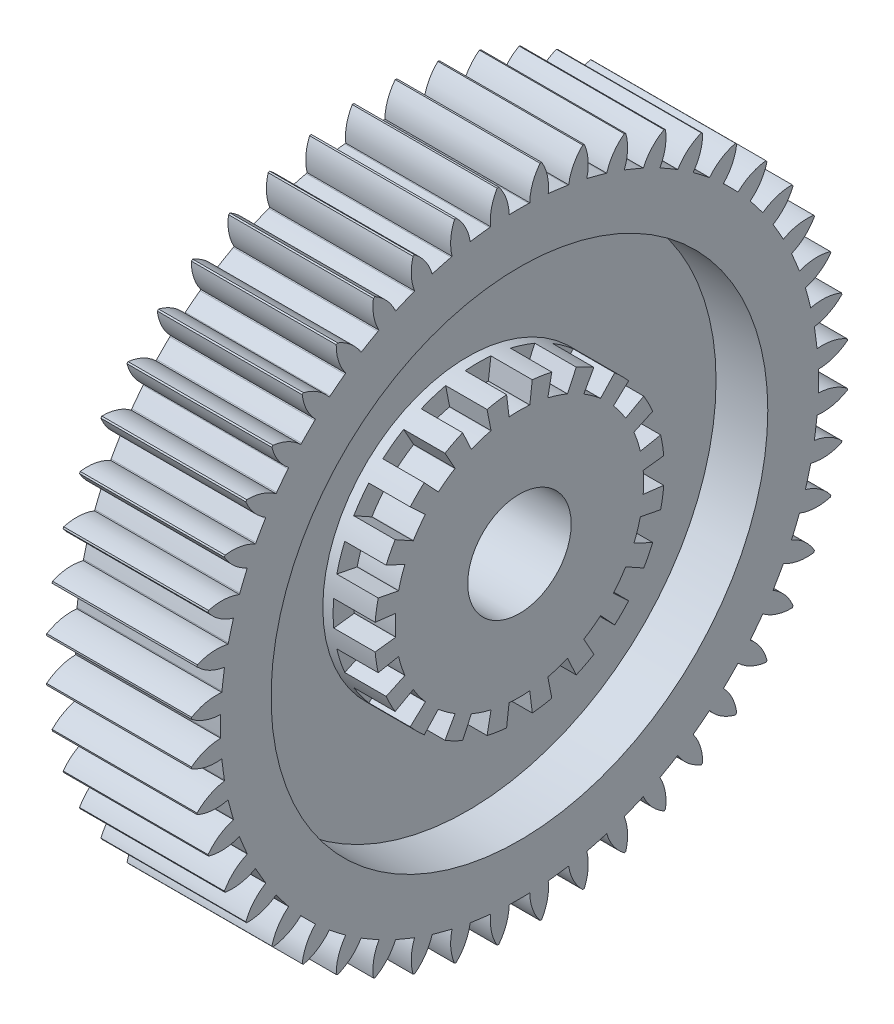
SolidWorks part; units mm, degrees
ref_plane "Front Plane" through (0, 0, 0) normal (0, 0, 1) x (1, 0, 0)
ref_plane "Top Plane" through (0, 0, 0) normal (0, 1, 0) x (1, 0, 0)
ref_plane "Right Plane" through (0, 0, 0) normal (1, 0, 0) x (0, 0, -1)
sketch "Sketch1" plane through (0, 0, 0) normal (1, 0, 0) x (0, 0, -1)
  circle A0 centre (0, 0) radius 158.75
  dimension "D1" = 317.5
extrude "Boss-Extrude1" add sketch "Sketch1" along normal mid plane 70
sketch "Sketch2" plane through (35, 0, 0) normal (1, 0, 0) x (0, 0, -1)
  circle A1 centre (0, 0) radius 25
  point P3 (0, 25)
  dimension "D1" = 50
extrude "Cut-Extrude1" cut sketch "Sketch2" against normal through all
sketch "Sketch3" plane through (35, 0, 0) normal (1, 0, 0) x (0, 0, -1)
  circle A0 centre (0, 0) radius 70
  circle A1 centre (0, 0) radius 120
  dimension "D1" = 140
  dimension "D2" = 240
extrude "Cut-Extrude2" cut sketch "Sketch3" against normal blind 25
sketch "Sketch4" plane through (35, 0, 0) normal (1, 0, 0) x (0, 0, -1)
  line L0 (0, 0) -> (0, 244.3511) construction
  line L1 (0, 144.465) -> (-4.985, 144.379)
  line L2 (0, 144.465) -> (4.985, 144.379)
  line L3 (-9.975, 158.4363) -> (0, 169.2356)
  line L4 (9.975, 158.4363) -> (0, 169.2356)
  circle A0 centre (0, 0) radius 152.4 construction
  circle A1 centre (0, 0) radius 144.465 construction
  arc A2 (-4.985, 144.379) -> (-9.975, 158.4363) centre (-28.4198, 143.9745) ccw
  circle A3 centre (0, 0) radius 158.75 construction
  arc A4 (4.985, 144.379) -> (9.975, 158.4363) centre (28.4198, 143.9745) cw
  dimension "D1" = 288.93
  dimension "D2" = 304.8
  dimension "D3" = 4.99
  dimension "D4" = 19.95
extrude "Cut-Extrude3" cut sketch "Sketch4" against normal through all
fillet "Fillet2" radius 260 1 edges at (0, 144.465, 0)
pattern_circular "CirPattern1" count 48 over 360 about axis through (35, 0, 0) along (1, 0, 0) of "Fillet2", "Cut-Extrude3"
sketch "Sketch6" plane through (35, 0, 0) normal (1, 0, 0) x (0, 0, -1)
  line L0 (0, 0) -> (0, 115.7105) construction
  line L4 (-5, 59.7913) -> (-10.3439, 103.7304)
  line L5 (5, 59.7913) -> (10.3439, 103.7304)
  line L6 (-10.3439, 103.7304) -> (10.3439, 103.7304)
  line L8 (-5, 59.7913) -> (0, 60.1942)
  line L9 (0, 60.1942) -> (5, 59.7913)
  circle A0 centre (0, 0) radius 60 construction
  dimension "D1" = 120
  dimension "D2" = 10
extrude "Cut-Extrude4" cut sketch "Sketch6" against normal blind 20
fillet "Fillet3" radius 60 1 edges at (25, 60.1942, 0)
pattern_circular "CirPattern2" count 20 over 360 about axis through (35, 0, 0) along (1, 0, 0) of "Fillet3", "Cut-Extrude4"
